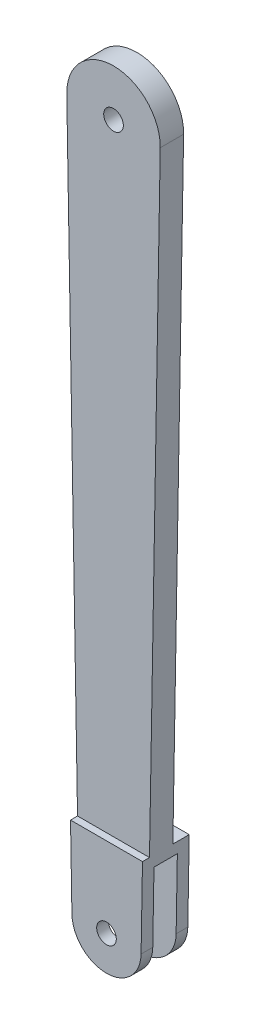
SolidWorks part; units mm, degrees
ref_plane "Front Plane" through (0, 0, 0) normal (0, 0, 1) x (1, 0, 0)
ref_plane "Top Plane" through (0, 0, 0) normal (0, 1, 0) x (1, 0, 0)
ref_plane "Right Plane" through (0, 0, 0) normal (1, 0, 0) x (0, 0, -1)
sketch "Sketch1" plane through (0, 0, 0) normal (0, 0, 1) x (1, 0, 0)
  line L0 (0, 75) -> (0, -75)
  line L1 (9.9985, 74.8267) -> (7.3989, -75.1283)
  line L2 (-9.9985, 74.8267) -> (-7.3989, -75.1283)
  line L3 (-7.6984, -57.8506) -> (7.6984, -57.8506)
  circle A0 centre (0, 75) radius 10
  circle A1 centre (0, -75) radius 7.4
  point P4 (0, 0)
extrude "Boss-Extrude1" add sketch "Sketch1" along normal mid plane 5 contours A0 | A1 L1 A0 L0 | A1 L0 A0 L2 | A1 region at (4.4647, 7.2108, 0) region at (-4.4647, 7.2108, 0) region at (-6.8113, 68.0696, 0) region at (5.0846, -69.9154, 0)
ref_axis "Axis1" through (0, 75, 19.6531) along (0, 0, -1)
ref_axis "Axis2" through (0, -75, 23.7794) along (0, 0, -1)
extrude "Boss-Extrude4" add sketch "Sketch1<6>" along normal blind 4 and the other way blind 10 contours A1 L0 L3 L2 | A1 | A1 L1 L3 L0 region at (4.0911, -63.6381, 0) region at (-4.0911, -63.6381, 0) region at (5.0846, -69.9154, 0)
sketch "Sketch1<6>" plane through (0, 0, 0) normal (0, 0, 1) x (1, 0, 0) same geometry as "Sketch1"
sketch "Sketch2" plane through (-8.6987, -0.1508, 0) normal (-0.9998, -0.0173, 0) x (0, 0, 1)
  line L0 (0, 74.6421) -> (0, -75.2452) construction
  line L1 (1.5, -60.2747) -> (-3.5, -60.2747)
  line L2 (1.5, -60.2747) -> (1.5, -85.6558)
  line L3 (1.5, -85.6558) -> (-3.5, -85.6558)
  line L4 (-3.5, -60.2747) -> (-3.5, -85.6558)
  point P4 (-1, -60.2747)
  dimension "D1" = 1
extrude "Cut-Extrude1" cut sketch "Sketch2" against normal blind 20
sketch "Sketch3" plane through (0, 0, -10) normal (0, 0, -1) x (-1, 0, 0)
  line L0 (-7.3989, -75.1283) -> (-7.6984, -57.8506)
  line L1 (-7.6984, -57.8506) -> (7.6984, -57.8506)
  line L2 (7.6984, -57.8506) -> (7.3989, -75.1283)
  circle A0 centre (0, -75) radius 7.4
  line M2 (7.3989, -75.1283) -> (7.6984, -57.8506)
  line M3 (7.6984, -57.8506) -> (-7.6984, -57.8506)
  line M4 (-7.6984, -57.8506) -> (-7.3989, -75.1283)
  arc M5 (-7.3989, -75.1283) -> (7.3989, -75.1283) centre (0, -75) ccw
extrude "Cut-Extrude2" cut sketch "Sketch3" against normal blind 4 contours A0 M2 M3 M4 | A0 M5 region at (0, -63.6381, -10) region at (0, -75, -10)
sketch "Sketch4" plane through (0, 0, 4) normal (0, 0, 1) x (1, 0, 0)
  circle A0 centre (0, 75) radius 2.1
  circle A1 centre (0, -75) radius 2.1
extrude "Cut-Extrude3" cut sketch "Sketch4" against normal through all
